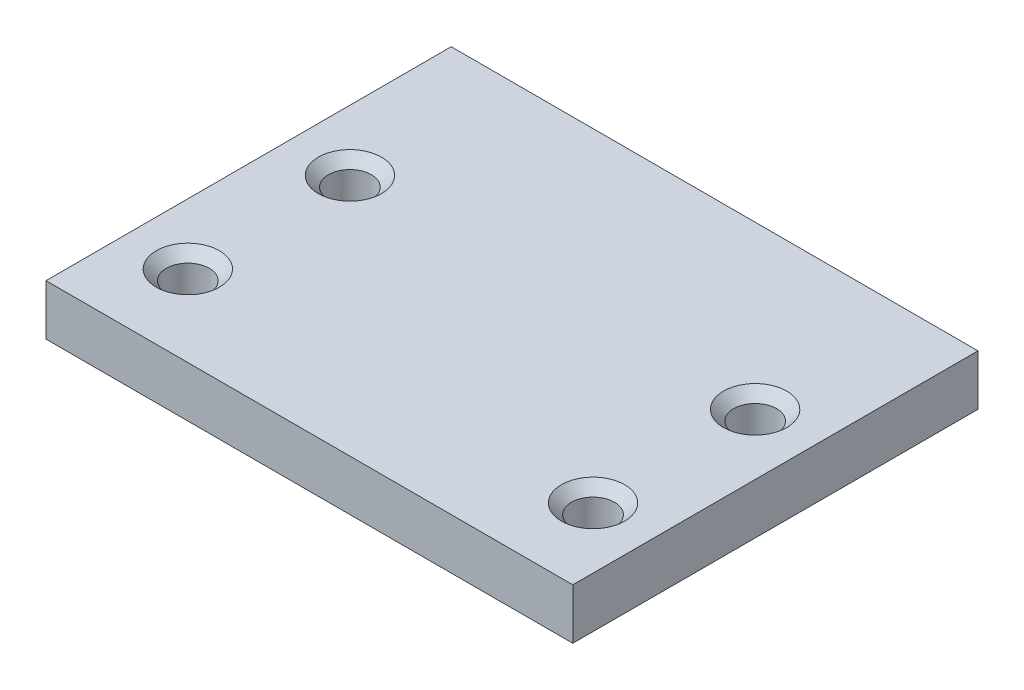
SolidWorks part; units mm, degrees
ref_plane "Front Plane" through (0, 0, 0) normal (0, 0, 1) x (1, 0, 0)
ref_plane "Top Plane" through (0, 0, 0) normal (0, 1, 0) x (1, 0, 0)
ref_plane "Right Plane" through (0, 0, 0) normal (1, 0, 0) x (0, 0, -1)
sketch "Sketch1" plane through (0, 0, 0) normal (0, 1, 0) x (1, 0, 0)
  line L0 (0, 0) -> (0, 46.1982) construction
  line L2 (26, 20) -> (-26, 20)
  line L3 (-26, 20) -> (-26, -20)
  line L4 (-26, -20) -> (26, -20)
  line L5 (26, 20) -> (26, -20)
  circle A0 centre (-20, 4) radius 2.12
  circle A1 centre (-20, 4) radius 2.75
  circle A2 centre (20, 4) radius 2.12
  circle A3 centre (20, 4) radius 2.75
  circle A4 centre (-20, -12) radius 2.12
  circle A5 centre (-20, -12) radius 2.75
  circle A6 centre (20, -12) radius 2.12
  circle A7 centre (20, -12) radius 2.75
  point P5 (-20, 4)
  point P6 (-20, -12)
  point P22 (0, 20)
  dimension "D2" = 0.63
  dimension "D7" = 6
  dimension "D1" = 16
  dimension "D3" = 26
  dimension "D5" = 6
  dimension "D6" = 16
  dimension "D8" = 8
extrude "Boss-Extrude10" add sketch "Sketch1" along normal blind 5 contours L5 L2 L3 L4 A5 A1 A3 A7 region at (0, 0, -0.1915)
extrude "Boss-Extrude13" add sketch "Sketch1<21>" along normal blind 5 contours A3
sketch "Sketch1<21>" plane through (0, 0, 0) normal (0, 1, 0) x (1, 0, 0) same geometry as "Sketch1"
extrude "Cut-Extrude4" cut sketch "Sketch1<22>" along normal blind 7 contours A2
sketch "Sketch1<22>" plane through (0, 0, 0) normal (0, 1, 0) x (1, 0, 0) same geometry as "Sketch1"
chamfer "Chamfer1" distance 1 angle 45 1 edges at (20, 5, -1.88)
extrude "Boss-Extrude14" add sketch "Sketch1<23>" along normal blind 5 contours A7
sketch "Sketch1<23>" plane through (0, 0, 0) normal (0, 1, 0) x (1, 0, 0) same geometry as "Sketch1"
extrude "Cut-Extrude6" cut sketch "Sketch1<24>" along normal blind 5 contours A6
sketch "Sketch1<24>" plane through (0, 0, 0) normal (0, 1, 0) x (1, 0, 0) same geometry as "Sketch1"
extrude "Boss-Extrude15" add sketch "Sketch1<25>" along normal blind 5 contours A5
sketch "Sketch1<25>" plane through (0, 0, 0) normal (0, 1, 0) x (1, 0, 0) same geometry as "Sketch1"
extrude "Cut-Extrude7" cut sketch "Sketch1<26>" along normal blind 18 contours A4
sketch "Sketch1<26>" plane through (0, 0, 0) normal (0, 1, 0) x (1, 0, 0) same geometry as "Sketch1"
extrude "Boss-Extrude17" add sketch "Sketch1<29>" along normal blind 5 contours A1
sketch "Sketch1<29>" plane through (0, 0, 0) normal (0, 1, 0) x (1, 0, 0) same geometry as "Sketch1"
extrude "Cut-Extrude9" cut sketch "Sketch1<30>" along normal blind 14 contours A0
sketch "Sketch1<30>" plane through (0, 0, 0) normal (0, 1, 0) x (1, 0, 0) same geometry as "Sketch1"
chamfer "Chamfer3" distance 1 angle 45 1 edges at (-20, 5, -1.88)
chamfer "Chamfer4" distance 1 angle 45 1 edges at (-20, 5, 14.12)
chamfer "Chamfer5" distance 1 angle 45 1 edges at (20, 5, 9.88)
